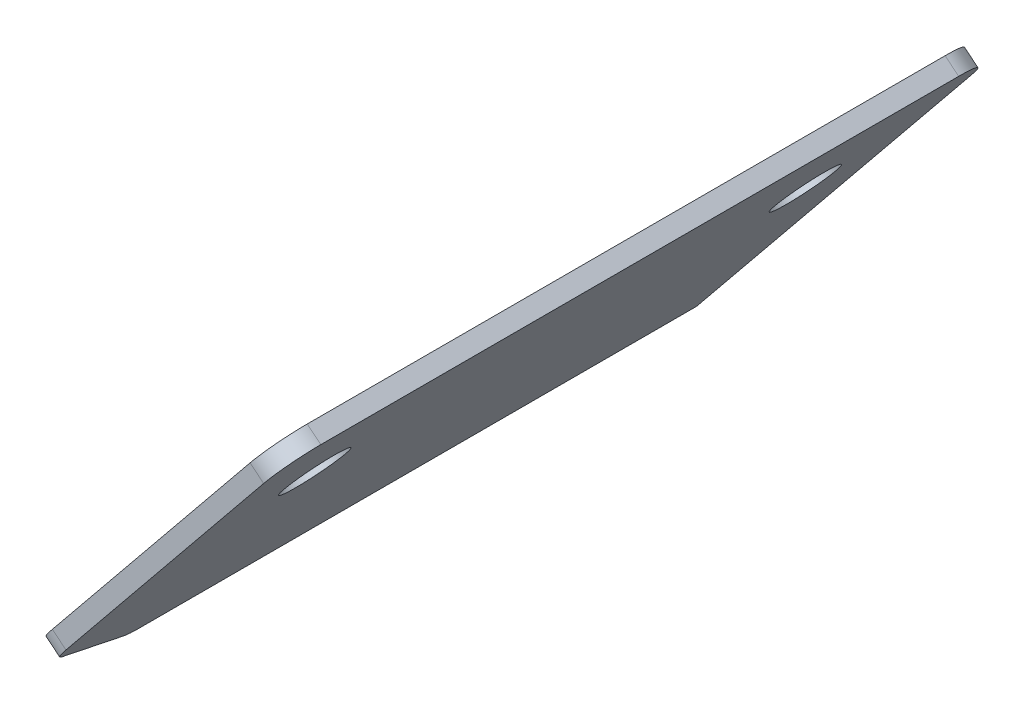
SolidWorks part; units mm, degrees
ref_plane "Front Plane" through (0, 0, 0) normal (0, 0, 1) x (1, 0, 0)
ref_plane "Top Plane" through (0, 0, 0) normal (0, 1, 0) x (1, 0, 0)
ref_plane "Right Plane" through (0, 0, 0) normal (1, 0, 0) x (0, 0, -1)
sketch "Sketch1" plane through (0, 0, 0) normal (0, 0, 1) x (1, 0, 0)
  line L0 (-455.1568, -418.287) -> (-562.8553, -550.6808)
  line L1 (-117.475, -3.175) -> (-519.2711, -497.1027) construction
  line L2 (-562.8553, -550.6808) -> (-567.7813, -546.6736)
  line L3 (-567.7813, -546.6736) -> (-460.0828, -414.2799)
  line L4 (-460.0828, -414.2799) -> (-455.1568, -418.287)
  circle A1 centre (-615.95, -615.95) radius 84.1375 construction
  point P8 (-519.2711, -497.1027)
  dimension "D1" = 6.35
  dimension "D2" = 101.6
extrude "Boss-Extrude1" add sketch "Sketch1" along normal up to surface (256.54 mm away)
sketch "Sketch2" plane through (-74.0659, 60.2505, 0) normal (-0.7757, 0.631, 0) x (0, 0, 1)
  line L0 (128.27, -611.7092) -> (121.92, -713.3092) construction
  line L1 (256.54, -611.7092) -> (0, -611.7092) construction
  line L2 (243.84, -713.3092) -> (0, -713.3092) construction
  line L3 (213.995, -662.5092) -> (36.195, -662.5092) construction
  circle A0 centre (213.995, -662.5092) radius 11.1125
  circle A1 centre (36.195, -662.5092) radius 11.1125
  point P8 (125.095, -662.5092)
  dimension "D2" = 22.225
  dimension "D1" = 177.8
extrude "Cut-Extrude1" cut sketch "Sketch2" against normal up to next
sketch "Sketch3" plane through (-69.1399, 56.2433, 0) normal (0.7757, -0.631, 0) x (0, 0, -1)
  line L0 (-205.74, -782.3757) -> (-256.54, -744.2757)
  line L1 (-256.54, -782.3757) -> (0, -782.3757) construction
  line L2 (-256.54, -782.3757) -> (-256.54, -611.7092) construction
  dimension "D1" = 50.8
  dimension "D2" = 38.1
extrude "Cut-Extrude2" cut sketch "Sketch3" against normal through all and the other way through all
fillet "Fillet1" radius 12.7 4 edges at (-541.2754, -519.1213, 256.54) (-565.3183, -548.6772, 205.74) (-457.6198, -416.2835, 0) (-457.6198, -416.2835, 256.54)
